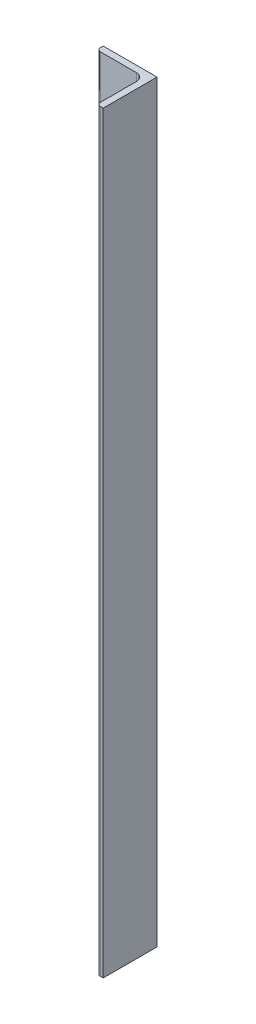
SolidWorks part; units mm, degrees
ref_plane "Front Plane" through (0, 0, 0) normal (0, 0, 1) x (1, 0, 0)
ref_plane "Top Plane" through (0, 0, 0) normal (0, 1, 0) x (1, 0, 0)
ref_plane "Right Plane" through (0, 0, 0) normal (1, 0, 0) x (0, 0, -1)
sketch "Sketch1" plane through (0, 0, 0) normal (0, 1, 0) x (1, 0, 0)
  line L6 (0, 0) -> (-50, 0)
  line L10 (0, 0) -> (0, -50)
  line L11 (0, -50) -> (-2.5, -50)
  line L12 (-50, 0) -> (-50, -2.5)
  line L15 (-46.5, -6) -> (-13, -6)
  line L16 (-6, -46.5) -> (-6, -13)
  arc A8 (-13, -6) -> (-6, -13) centre (-13, -13) cw
  arc A9 (-2.5, -50) -> (-6, -46.5) centre (-2.5, -46.5) cw
  arc A10 (-50, -2.5) -> (-46.5, -6) centre (-46.5, -2.5) ccw
  dimension "D4" = 6
  dimension "D5" = 7
  dimension "D6" = 3.5
  dimension "D1" = 50
  dimension "D2" = 50
  dimension "D3" = 6
extrude "Boss-Extrude1" add sketch "Sketch1" along normal mid plane 700
sketch "Sketch2" plane through (0, 0, 0) normal (0, 0, -1) x (-1, 0, 0)
  line L0 (50, 350) -> (50, -350) construction
  line L1 (55, 0) -> (-55, 0) construction
  circle A0 centre (30, 52.92) radius 6
  circle A1 centre (30, -52.92) radius 6
  dimension "D1" = 12
  dimension "D2" = 20
  dimension "D3" = 52.92
extrude "Cut-Extrude1" cut sketch "Sketch2" against normal up to next
